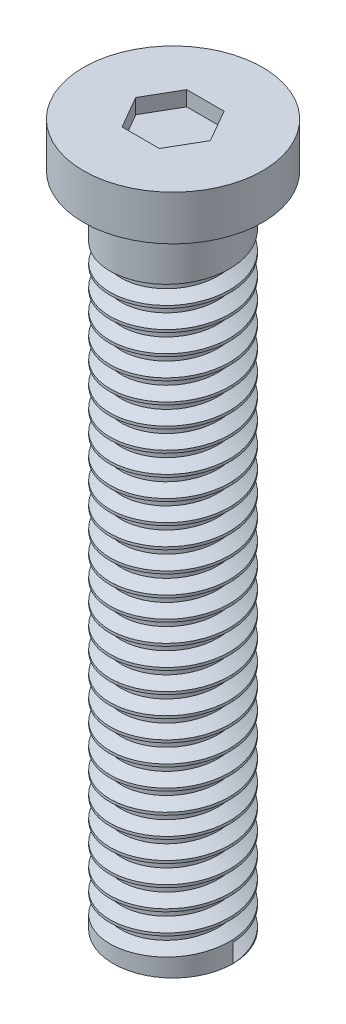
SolidWorks part; units mm, degrees
ref_plane "Front" through (0, 0, 0) normal (0, 0, 1) x (1, 0, 0)
ref_plane "Top" through (0, 0, 0) normal (0, 1, 0) x (1, 0, 0)
ref_plane "Right" through (0, 0, 0) normal (1, 0, 0) x (0, 0, -1)
sketch "Sketch1" plane through (0, 0, 0) normal (0, 1, 0) x (1, 0, 0)
  circle A0 centre (0, 0) radius 2
  dimension "D1" = 4
extrude "Boss-Extrude1" add sketch "Sketch1" along normal blind 22
sketch "Sketch2" plane through (0, 22, 0) normal (0, 1, 0) x (1, 0, 0)
  circle A1 centre (0, 0) radius 3
  dimension "D1" = 6
extrude "Boss-Extrude2" add sketch "Sketch2" along normal blind 1.5
sketch "Sketch3" plane through (0, 23.5, 0) normal (0, 1, 0) x (1, 0, 0)
  line L1 (0.625, -1.0825) -> (1.25, 0)
  line L2 (1.25, 0) -> (0.625, 1.0825)
  line L3 (0.625, 1.0825) -> (-0.625, 1.0825)
  line L4 (-0.625, 1.0825) -> (-1.25, 0)
  line L5 (-1.25, 0) -> (-0.625, -1.0825)
  line L6 (-0.625, -1.0825) -> (0.625, -1.0825)
  circle A0 centre (0, 0) radius 1.0825 construction
  dimension "D1" = 1.25
extrude "Cut-Extrude1" cut sketch "Sketch3" against normal blind 0.5
thread "Thread1" pitch 0.7 method cut profile "Thread Profile1" start angle 0, offset 0, length 20, pitch 0.7, diameter 4
ref_plane "Plane1" through (2, 0, 0) normal (0, 0, 1) x (1, 0, 0)
sketch "Thread Profile1" plane through (2, 0, 0) normal (0, 0, 1) x (1, 0, 0)
  line L0 (0, 0) -> (0, 0.7) construction
  line L11 (0, 0) -> (0, 0.6125)
  line L12 (0, 0.6125) -> (-0.3789, 0.3937)
  line L13 (-0.3789, 0.3937) -> (-0.3789, 0.2187)
  line L15 (-0.3789, 0.2187) -> (0, 0)
  line L17 (-0.3789, 0.3062) -> (0, 0.3062) construction
  point P2 (0, 0)
  dimension "Pitch" = 0.7
  dimension "Profile_Angle" = 60
  dimension "Profile_Land" = 0.175
  dimension "Profile_Height" = 0.3789
